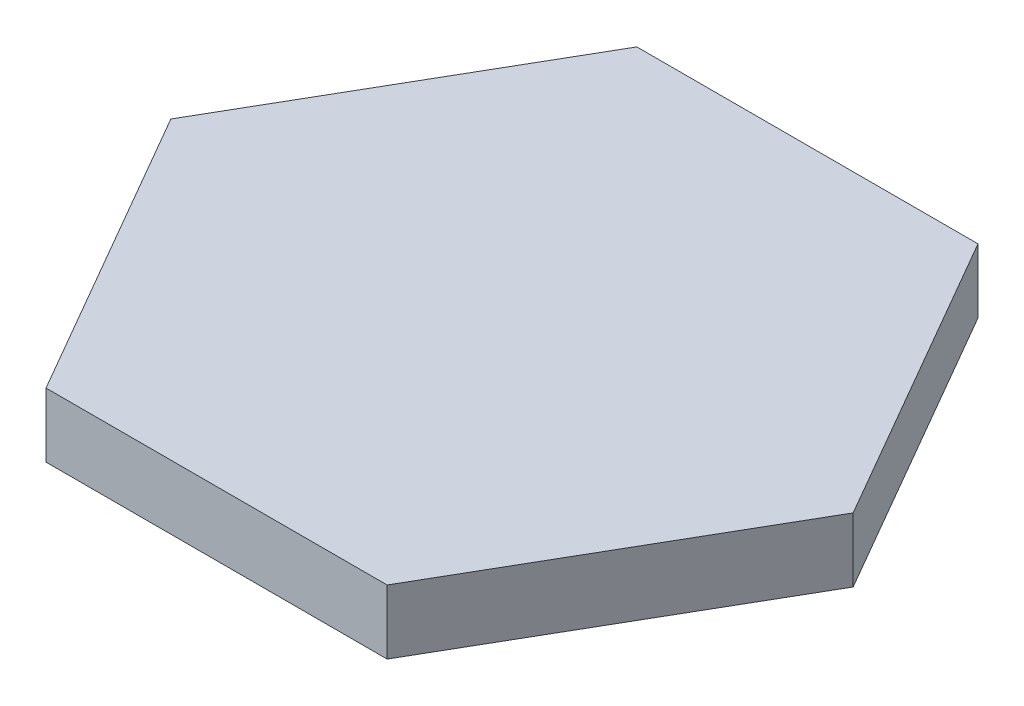
SolidWorks part; units mm, degrees
ref_plane "Front Plane" through (0, 0, 0) normal (0, 0, 1) x (1, 0, 0)
ref_plane "Top Plane" through (0, 0, 0) normal (0, 1, 0) x (1, 0, 0)
ref_plane "Right Plane" through (0, 0, 0) normal (1, 0, 0) x (0, 0, -1)
sketch "Sketch1" plane through (0, 0, 0) normal (0, 1, 0) x (1, 0, 0)
  line L1 (13.5, -23.3827) -> (27, 0)
  line L2 (27, 0) -> (13.5, 23.3827)
  line L3 (13.5, 23.3827) -> (-13.5, 23.3827)
  line L4 (-13.5, 23.3827) -> (-27, 0)
  line L5 (-27, 0) -> (-13.5, -23.3827)
  line L6 (-13.5, -23.3827) -> (13.5, -23.3827)
  circle A0 centre (0, 0) radius 23.3827 construction
  dimension "D1" = 27
extrude "Boss-Extrude1" add sketch "Sketch1" along normal blind 5.08 contours L4 L5 L6 L1 L2 L3
sketch "Sketch2" plane through (0, 0, 0) normal (0, -1, 0) x (1, 0, 0)
  line L1 (3.175, 7) -> (-3.175, 7)
  line L2 (3.175, 7) -> (3.175, 13.35)
  line L3 (3.175, 13.35) -> (-3.175, 13.35)
  line L4 (-3.175, 7) -> (-3.175, 13.35)
  circle A0 centre (0, 0) radius 5.5
  circle A1 centre (0, 0) radius 8.5
  point P9 (-4.2793, 7.9338)
  point P10 (0, 13.35)
  dimension "D1" = 11
  dimension "D3" = 6.35
  dimension "D4" = 1.5
  dimension "D2" = 3
